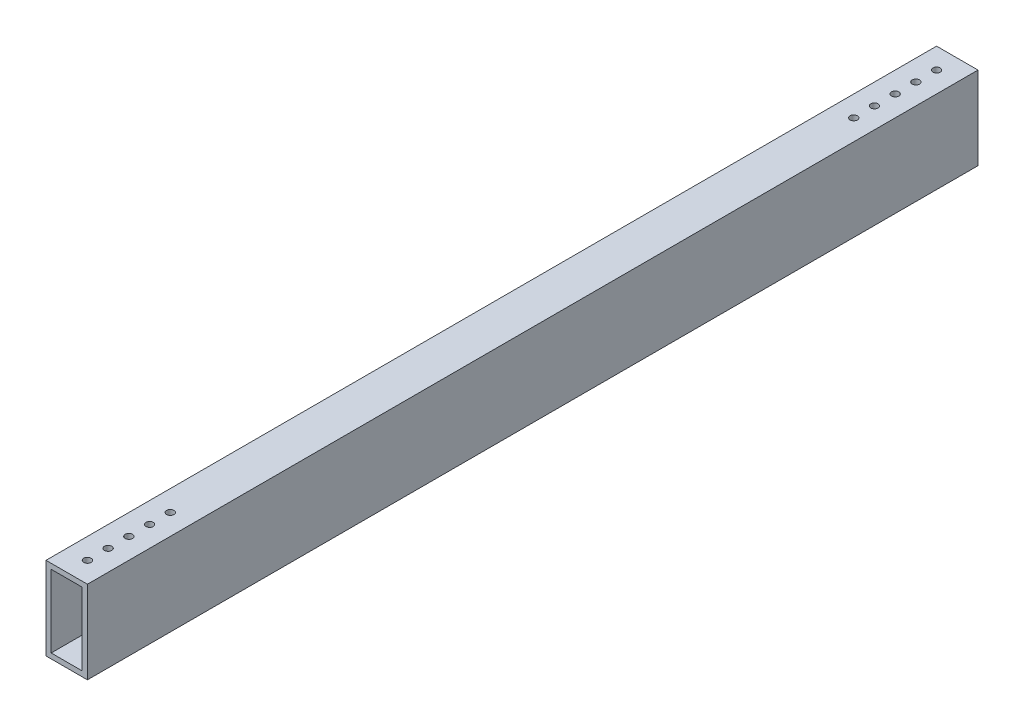
SolidWorks part; units mm, degrees
material "1060 Alloy"
ref_plane "Front Plane" through (0, 0, 0) normal (0, 0, 1) x (1, 0, 0)
ref_plane "Top Plane" through (0, 0, 0) normal (0, 1, 0) x (1, 0, 0)
ref_plane "Right Plane" through (0, 0, 0) normal (1, 0, 0) x (0, 0, -1)
sketch "Sketch1" plane through (0, 0, 0) normal (0, 0, 1) x (1, 0, 0)
  line L0 (3.175, 47.625) -> (22.225, 47.625)
  line L1 (0, 0) -> (25.4, 0)
  line L2 (0, 0) -> (0, 50.8)
  line L3 (0, 50.8) -> (25.4, 50.8)
  line L4 (25.4, 0) -> (25.4, 50.8)
  line L5 (22.225, 3.175) -> (22.225, 47.625)
  line L6 (3.175, 3.175) -> (22.225, 3.175)
  line L7 (3.175, 3.175) -> (3.175, 47.625)
  dimension "D1" = 25.4
  dimension "D2" = 50.8
  dimension "D3" = 3.175
extrude "Boss-Extrude1" add sketch "Sketch1" along normal mid plane 546.1
sketch "Sketch2" plane through (0, 0, 0) normal (0, 1, 0) x (1, 0, 0)
  line L0 (0, 260.35) -> (25.4, 260.35) construction
  line L1 (25.4, -273.05) -> (25.4, 273.05) construction
  line L2 (0, -273.05) -> (0, 273.05) construction
  line L4 (0, 273.05) -> (25.4, 273.05) construction
  circle A0 centre (12.7, 260.35) radius 2.2479
  circle A7 centre (12.7, 247.65) radius 2.2479
  circle A8 centre (12.7, 234.95) radius 2.2479
  circle A12 centre (12.7, 222.25) radius 2.2479
  circle A13 centre (12.7, 209.55) radius 2.2479
  point P7 (12.7, 260.35)
  dimension "D1" = 4.4958
  dimension "D2" = 12.7
  dimension "D3" = 12.7
extrude "Cut-Extrude5" cut sketch "Sketch2" along normal up to next contours A0 | A8 | A13 region at (12.7, 0, -260.35) region at (12.7, 0, -234.95) region at (12.7, 0, -209.55)
extrude "Cut-Extrude9" cut sketch "Sketch2<5>" along normal through all from surface contours A0 L0 | L0 A0 | A7 | A8 | A12 | A13 region at (12.7, 0, -261.304) region at (12.7, 0, -259.396) region at (12.7, 0, -247.65) region at (12.7, 0, -234.95) region at (12.7, 0, -222.25) region at (12.7, 0, -209.55) starting at face at (12.7, 3.175, -258.1021)
sketch "Sketch2<5>" plane through (0, 0, 0) normal (0, 1, 0) x (1, 0, 0) same geometry as "Sketch2"
mirror "Mirror3" about plane through (0, 0, 0) normal (0, 0, 1) of "Cut-Extrude5", "Cut-Extrude9"
sketch "Sketch4" plane through (0, 50.8, 0) normal (0, 1, 0) x (1, 0, 0)
  circle A0 centre (12.7, 50.8) radius 3.2639 construction
  circle A1 centre (12.7, 95.25) radius 3.2639 construction
  circle A2 centre (12.7, 184.15) radius 3.2639 construction
  circle A3 centre (12.7, -50.8) radius 3.2639 construction
  circle A4 centre (12.7, -95.25) radius 3.2639 construction
  circle A5 centre (12.7, -184.15) radius 3.2639 construction
  circle A6 centre (12.7, 50.8) radius 3.2639
  circle A7 centre (12.7, 95.25) radius 3.2639
  circle A8 centre (12.7, 184.15) radius 3.2639
  circle A9 centre (12.7, -50.8) radius 3.2639
  circle A10 centre (12.7, -95.25) radius 3.2639
  circle A11 centre (12.7, -184.15) radius 3.2639
extrude "Cut-Extrude12" [suppressed] cut sketch "Sketch4" against normal up to surface (50.8 mm away)
